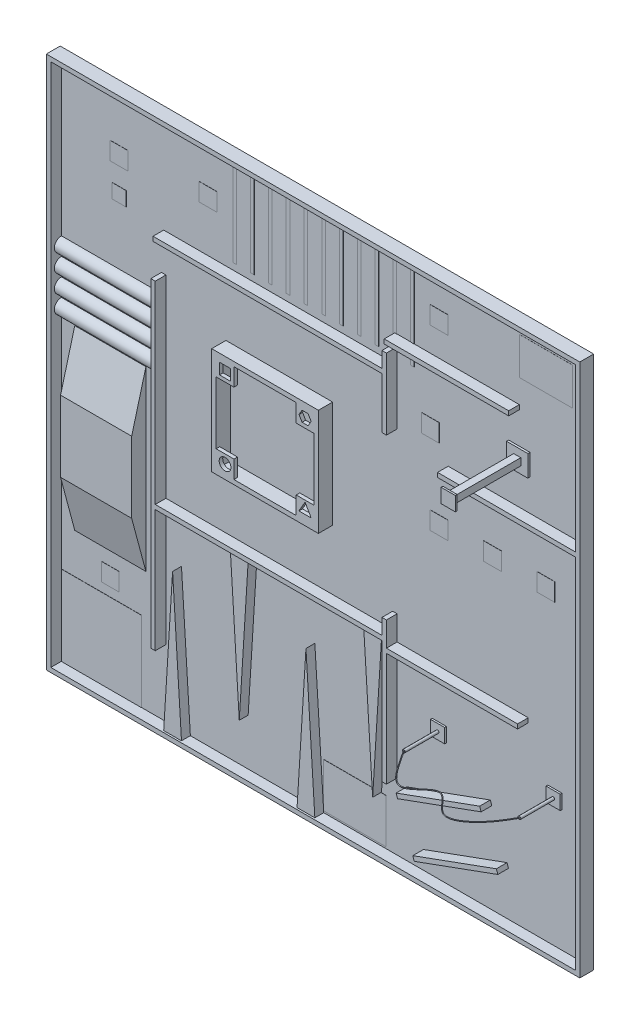
SolidWorks part; units mm, degrees
ref_plane "Front Plane" through (0, 0, 0) normal (0, 0, 1) x (1, 0, 0)
ref_plane "Top Plane" through (0, 0, 0) normal (0, 1, 0) x (1, 0, 0)
ref_plane "Right Plane" through (0, 0, 0) normal (1, 0, 0) x (0, 0, -1)
ref_plane "P_Front_m18" through (0, 0, -18) normal (0, 0, 1) x (1, 0, 0)
sketch "Sketch1" plane through (0, 0, -18) normal (0, 0, 1) x (1, 0, 0)
  line L0 (-1500, -1500) -> (1500, -1500)
  line L1 (1500, -1500) -> (1500, 1500)
  line L2 (1500, 1500) -> (-1500, 1500)
  line L3 (-1500, 1500) -> (-1500, -1500)
extrude "Board_18mm_ply" add sketch "Sketch1" along normal blind 18
sketch "Sketch2" plane through (0, 0, 0) normal (0, 0, 1) x (1, 0, 0)
  line L0 (-1500, -1500) -> (1500, -1500)
  line L1 (1500, -1500) -> (1500, 1500)
  line L2 (1500, 1500) -> (-1500, 1500)
  line L3 (-1500, 1500) -> (-1500, -1500)
  line L4 (-1475, -1475) -> (1475, -1475)
  line L5 (1475, -1475) -> (1475, 1475)
  line L6 (1475, 1475) -> (-1475, 1475)
  line L7 (-1475, 1475) -> (-1475, -1475)
extrude "Perimeter_wall" add sketch "Sketch2" along normal blind 60
sketch "Sketch3" plane through (0, 0, 0) normal (0, 0, 1) x (1, 0, 0)
  line L0 (-912.5, -1100) -> (-887.5, -1100)
  line L1 (-887.5, -1100) -> (-887.5, 700)
  line L2 (-887.5, 700) -> (-912.5, 700)
  line L3 (-912.5, 700) -> (-912.5, -1100)
extrude "Wall_1" add sketch "Sketch3" along normal blind 60
sketch "Sketch4" plane through (0, 0, 0) normal (0, 0, 1) x (1, 0, 0)
  line L0 (-900, 887.5) -> (400, 887.5)
  line L1 (400, 887.5) -> (400, 912.5)
  line L2 (400, 912.5) -> (-900, 912.5)
  line L3 (-900, 912.5) -> (-900, 887.5)
extrude "Wall_2" add sketch "Sketch4" along normal blind 60
sketch "Sketch5" plane through (0, 0, 0) normal (0, 0, 1) x (1, 0, 0)
  line L0 (387.5, 600) -> (412.5, 600)
  line L1 (412.5, 600) -> (412.5, 1000)
  line L2 (412.5, 1000) -> (387.5, 1000)
  line L3 (387.5, 1000) -> (387.5, 600)
extrude "Wall_3" add sketch "Sketch5" along normal blind 60
sketch "Sketch6" plane through (0, 0, 0) normal (0, 0, 1) x (1, 0, 0)
  line L0 (387.5, -1100) -> (412.5, -1100)
  line L1 (412.5, -1100) -> (412.5, -300)
  line L2 (412.5, -300) -> (387.5, -300)
  line L3 (387.5, -300) -> (387.5, -1100)
extrude "Wall_4" add sketch "Sketch6" along normal blind 60
sketch "Sketch7" plane through (0, 0, 0) normal (0, 0, 1) x (1, 0, 0)
  line L0 (400, 1037.5) -> (1100, 1037.5)
  line L1 (1100, 1037.5) -> (1100, 1062.5)
  line L2 (1100, 1062.5) -> (400, 1062.5)
  line L3 (400, 1062.5) -> (400, 1037.5)
extrude "Wall_5" add sketch "Sketch7" along normal blind 60
sketch "Sketch8" plane through (0, 0, 0) normal (0, 0, 1) x (1, 0, 0)
  line L0 (700, 537.5) -> (1475, 537.5)
  line L1 (1475, 537.5) -> (1475, 562.5)
  line L2 (1475, 562.5) -> (700, 562.5)
  line L3 (700, 562.5) -> (700, 537.5)
extrude "Wall_6" add sketch "Sketch8" along normal blind 60
sketch "Sketch9" plane through (0, 0, 0) normal (0, 0, 1) x (1, 0, 0)
  line L0 (400, -462.5) -> (1150, -462.5)
  line L1 (1150, -462.5) -> (1150, -437.5)
  line L2 (1150, -437.5) -> (400, -437.5)
  line L3 (400, -437.5) -> (400, -462.5)
extrude "Wall_7" add sketch "Sketch9" along normal blind 60
sketch "Sketch10" plane through (0, 0, 0) normal (0, 0, 1) x (1, 0, 0)
  line L0 (-900, -412.5) -> (387.5, -412.5)
  line L1 (387.5, -412.5) -> (387.5, -387.5)
  line L2 (387.5, -387.5) -> (-900, -387.5)
  line L3 (-900, -387.5) -> (-900, -412.5)
extrude "Wall_8" add sketch "Sketch10" along normal blind 60
sketch "Sketch11" plane through (0, 0, 0) normal (0, 0, 1) x (1, 0, 0)
  line L0 (569.3521, -1397.2512) -> (1039.1984, -1226.2411)
  line L1 (1039.1984, -1226.2411) -> (1030.6479, -1202.7488)
  line L2 (1030.6479, -1202.7488) -> (560.8016, -1373.7589)
  line L3 (560.8016, -1373.7589) -> (569.3521, -1397.2512)
extrude "Diagonal_1" add sketch "Sketch11" along normal blind 60
sketch "Sketch12" plane through (0, 0, 0) normal (0, 0, 1) x (1, 0, 0)
  line L0 (475.3521, -1139.2512) -> (945.1984, -968.2411)
  line L1 (945.1984, -968.2411) -> (936.6479, -944.7488)
  line L2 (936.6479, -944.7488) -> (466.8016, -1115.7589)
  line L3 (466.8016, -1115.7589) -> (475.3521, -1139.2512)
extrude "Diagonal_2" add sketch "Sketch12" along normal blind 60
sketch "Sketch13" plane through (0, 0, 0) normal (0, 0, 1) x (1, 0, 0)
  line L0 (-850, -1475) -> (-750, -1475)
  line L1 (-750, -1475) -> (-800, -675)
  line L2 (-800, -675) -> (-850, -1475)
extrude "Slalom_ridge_1" add sketch "Sketch13" along normal blind 50
sketch "Sketch14" plane through (0, 0, 0) normal (0, 0, 1) x (1, 0, 0)
  line L0 (-475, -412.5) -> (-375, -412.5)
  line L1 (-375, -412.5) -> (-425, -1212.5)
  line L2 (-425, -1212.5) -> (-475, -412.5)
extrude "Slalom_ridge_2" add sketch "Sketch14" along normal blind 50
sketch "Sketch15" plane through (0, 0, 0) normal (0, 0, 1) x (1, 0, 0)
  line L0 (-100, -1475) -> (0, -1475)
  line L1 (0, -1475) -> (-50, -675)
  line L2 (-50, -675) -> (-100, -1475)
extrude "Slalom_ridge_3" add sketch "Sketch15" along normal blind 50
sketch "Sketch16" plane through (0, 0, 0) normal (0, 0, 1) x (1, 0, 0)
  line L0 (275, -412.5) -> (375, -412.5)
  line L1 (375, -412.5) -> (325, -1212.5)
  line L2 (325, -1212.5) -> (275, -412.5)
extrude "Slalom_ridge_4" add sketch "Sketch16" along normal blind 50
sketch "Sketch17" plane through (0, 0, 0) normal (0, 0, 1) x (1, 0, 0)
  line L0 (-1475, -1475) -> (-1025, -1475)
  line L1 (-1025, -1475) -> (-1025, -1025)
  line L2 (-1025, -1025) -> (-1475, -1025)
  line L3 (-1475, -1025) -> (-1475, -1475)
extrude "Zone_Start" add sketch "Sketch17" along normal blind 1
sketch "Sketch18" plane through (0, 0, 0) normal (0, 0, 1) x (1, 0, 0)
  line L0 (-1250, -975) -> (-1150, -975)
  line L1 (-1150, -975) -> (-1150, -875)
  line L2 (-1150, -875) -> (-1250, -875)
  line L3 (-1250, -875) -> (-1250, -975)
extrude "Zone_Pickup_spot" add sketch "Sketch18" along normal blind 1
sketch "Sketch19" plane through (0, 0, 0) normal (0, 0, 1) x (1, 0, 0)
  line L0 (-1190, 920) -> (-1110, 920)
  line L1 (-1110, 920) -> (-1110, 1000)
  line L2 (-1110, 1000) -> (-1190, 1000)
  line L3 (-1190, 1000) -> (-1190, 920)
extrude "Zone_Touchdown_80" add sketch "Sketch19" along normal blind 1
sketch "Sketch20" plane through (0, 0, 0) normal (0, 0, 1) x (1, 0, 0)
  line L0 (-1200, 1100) -> (-1100, 1100)
  line L1 (-1100, 1100) -> (-1100, 1200)
  line L2 (-1100, 1200) -> (-1200, 1200)
  line L3 (-1200, 1200) -> (-1200, 1100)
extrude "Zone_Stack_100" add sketch "Sketch20" along normal blind 1
sketch "Sketch21" plane through (0, 0, 0) normal (0, 0, 1) x (1, 0, 0)
  line L0 (-700, 1150) -> (-600, 1150)
  line L1 (-600, 1150) -> (-600, 1250)
  line L2 (-600, 1250) -> (-700, 1250)
  line L3 (-700, 1250) -> (-700, 1150)
extrude "Zone_Longshot_spot" add sketch "Sketch21" along normal blind 1
sketch "Sketch22" plane through (0, 0, 0) normal (0, 0, 1) x (1, 0, 0)
  line L0 (600, 1200) -> (700, 1200)
  line L1 (700, 1200) -> (700, 1300)
  line L2 (700, 1300) -> (600, 1300)
  line L3 (600, 1300) -> (600, 1200)
extrude "Zone_Marker_spot" add sketch "Sketch22" along normal blind 1
sketch "Sketch23" plane through (0, 0, 0) normal (0, 0, 1) x (1, 0, 0)
  line L0 (550, 650) -> (650, 650)
  line L1 (650, 650) -> (650, 750)
  line L2 (650, 750) -> (550, 750)
  line L3 (550, 750) -> (550, 650)
extrude "Zone_Downy_target" add sketch "Sketch23" along normal blind 1
sketch "Sketch24" plane through (0, 0, 0) normal (0, 0, 1) x (1, 0, 0)
  line L0 (600, 200) -> (700, 200)
  line L1 (700, 200) -> (700, 300)
  line L2 (700, 300) -> (600, 300)
  line L3 (600, 300) -> (600, 200)
extrude "Zone_Hanoi_1" add sketch "Sketch24" along normal blind 1
sketch "Sketch25" plane through (0, 0, 0) normal (0, 0, 1) x (1, 0, 0)
  line L0 (900, 200) -> (1000, 200)
  line L1 (1000, 200) -> (1000, 300)
  line L2 (1000, 300) -> (900, 300)
  line L3 (900, 300) -> (900, 200)
extrude "Zone_Hanoi_2" add sketch "Sketch25" along normal blind 1
sketch "Sketch26" plane through (0, 0, 0) normal (0, 0, 1) x (1, 0, 0)
  line L0 (1200, 200) -> (1300, 200)
  line L1 (1300, 200) -> (1300, 300)
  line L2 (1300, 300) -> (1200, 300)
  line L3 (1200, 300) -> (1200, 200)
extrude "Zone_Hanoi_3" add sketch "Sketch26" along normal blind 1
sketch "Sketch27" plane through (0, 0, 0) normal (0, 0, 1) x (1, 0, 0)
  line L0 (0, -1465) -> (350, -1465)
  line L1 (350, -1465) -> (350, -1215)
  line L2 (350, -1215) -> (0, -1215)
  line L3 (0, -1215) -> (0, -1465)
extrude "Zone_End_350x250" add sketch "Sketch27" along normal blind 1
sketch "Sketch28" plane through (0, 0, 0) normal (0, 0, 1) x (1, 0, 0)
  line L0 (-510, 950) -> (-490, 950)
  line L1 (-490, 950) -> (-490, 1450)
  line L2 (-490, 1450) -> (-510, 1450)
  line L3 (-510, 1450) -> (-510, 950)
  line L4 (-410, 950) -> (-390, 950)
  line L5 (-390, 950) -> (-390, 1450)
  line L6 (-390, 1450) -> (-410, 1450)
  line L7 (-410, 1450) -> (-410, 950)
  line L8 (-310, 950) -> (-290, 950)
  line L9 (-290, 950) -> (-290, 1450)
  line L10 (-290, 1450) -> (-310, 1450)
  line L11 (-310, 1450) -> (-310, 950)
  line L12 (-210, 950) -> (-190, 950)
  line L13 (-190, 950) -> (-190, 1450)
  line L14 (-190, 1450) -> (-210, 1450)
  line L15 (-210, 1450) -> (-210, 950)
  line L16 (-110, 950) -> (-90, 950)
  line L17 (-90, 950) -> (-90, 1450)
  line L18 (-90, 1450) -> (-110, 1450)
  line L19 (-110, 1450) -> (-110, 950)
  line L20 (-10, 950) -> (10, 950)
  line L21 (10, 950) -> (10, 1450)
  line L22 (10, 1450) -> (-10, 1450)
  line L23 (-10, 1450) -> (-10, 950)
  line L24 (90, 950) -> (110, 950)
  line L25 (110, 950) -> (110, 1450)
  line L26 (110, 1450) -> (90, 1450)
  line L27 (90, 1450) -> (90, 950)
  line L28 (190, 950) -> (210, 950)
  line L29 (210, 950) -> (210, 1450)
  line L30 (210, 1450) -> (190, 1450)
  line L31 (190, 1450) -> (190, 950)
  line L32 (290, 950) -> (310, 950)
  line L33 (310, 950) -> (310, 1450)
  line L34 (310, 1450) -> (290, 1450)
  line L35 (290, 1450) -> (290, 950)
  line L36 (390, 950) -> (410, 950)
  line L37 (410, 950) -> (410, 1450)
  line L38 (410, 1450) -> (390, 1450)
  line L39 (390, 1450) -> (390, 950)
  line L40 (490, 950) -> (510, 950)
  line L41 (510, 950) -> (510, 1450)
  line L42 (510, 1450) -> (490, 1450)
  line L43 (490, 1450) -> (490, 950)
extrude "Longshot_lines_100mm" add sketch "Sketch28" along normal blind 1
sketch "Sketch29" plane through (0, 0, 0) normal (0, 0, 1) x (1, 0, 0)
  line L0 (1101.5, 1195) -> (1398.5, 1195)
  line L1 (1398.5, 1195) -> (1398.5, 1405)
  line L2 (1398.5, 1405) -> (1101.5, 1405)
  line L3 (1101.5, 1405) -> (1101.5, 1195)
extrude "Paper_A4_TF" add sketch "Sketch29" along normal blind 0.5
ref_plane "P_Right_m1400" through (-1400, 0, 0) normal (1, 0, 0) x (0, 0, -1)
sketch "Sketch30" plane through (-1400, 0, 0) normal (1, 0, 0) x (0, 0, -1)
  line L0 (0, -800) -> (-80, -501.4359)
  line L1 (-80, -501.4359) -> (-80, -101.4359)
  line L2 (-80, -101.4359) -> (0, 197.1281)
  line L3 (0, 197.1281) -> (0, -800)
extrude "Ramp_15deg_bridge_400" add sketch "Sketch30" along normal blind 400
ref_plane "P_Right_m1475" through (-1475, 0, 0) normal (1, 0, 0) x (0, 0, -1)
sketch "Sketch31" plane through (-1475, 0, 0) normal (1, 0, 0) x (0, 0, -1)
  line L0 (0, 217.1281) -> (0, 297.1281)
  line L1 (0, 317.1281) -> (0, 397.1281)
  line L2 (0, 417.1281) -> (0, 497.1281)
  line L3 (0, 517.1281) -> (0, 597.1281)
  arc A0 (0, 297.1281) -> (0, 217.1281) centre (0, 257.1281) ccw
  arc A1 (0, 397.1281) -> (0, 317.1281) centre (0, 357.1281) ccw
  arc A2 (0, 497.1281) -> (0, 417.1281) centre (0, 457.1281) ccw
  arc A3 (0, 597.1281) -> (0, 517.1281) centre (0, 557.1281) ccw
extrude "Speed_breakers_R40" add sketch "Sketch31" along normal blind 562.5
sketch "Sketch32" plane through (0, 0, 0) normal (0, 0, 1) x (1, 0, 0)
  line L0 (1040, 740) -> (1160, 740)
  line L1 (1160, 740) -> (1160, 860)
  line L2 (1160, 860) -> (1040, 860)
  line L3 (1040, 860) -> (1040, 740)
extrude "Pole_foot" add sketch "Sketch32" along normal blind 12
ref_plane "P_Front_12" through (0, 0, 12) normal (0, 0, 1) x (1, 0, 0)
sketch "Sketch33" plane through (0, 0, 12) normal (0, 0, 1) x (1, 0, 0)
  line L0 (1080, 780) -> (1120, 780)
  line L1 (1120, 780) -> (1120, 820)
  line L2 (1120, 820) -> (1080, 820)
  line L3 (1080, 820) -> (1080, 780)
extrude "Pole_post" add sketch "Sketch33" along normal blind 378
ref_plane "P_Front_390" through (0, 0, 390) normal (0, 0, 1) x (1, 0, 0)
sketch "Sketch34" plane through (0, 0, 390) normal (0, 0, 1) x (1, 0, 0)
  line L0 (1060, 760) -> (1140, 760)
  line L1 (1140, 760) -> (1140, 840)
  line L2 (1140, 840) -> (1060, 840)
  line L3 (1060, 840) -> (1060, 760)
extrude "Pole_top_400" add sketch "Sketch34" along normal blind 10
sketch "Sketch35" plane through (0, 0, 0) normal (0, 0, 1) x (1, 0, 0)
  line L0 (-550, -50) -> (50, -50)
  line L1 (50, -50) -> (50, 550)
  line L2 (50, 550) -> (-550, 550)
  line L3 (-550, 550) -> (-550, -50)
  line L4 (-525, -25) -> (25, -25)
  line L5 (25, -25) -> (25, 525)
  line L6 (25, 525) -> (-525, 525)
  line L7 (-525, 525) -> (-525, -25)
extrude "Escape_box_600" add sketch "Sketch35" along normal blind 80
ref_plane "P_Front_60" through (0, 0, 60) normal (0, 0, 1) x (1, 0, 0)
sketch "Sketch36" plane through (0, 0, 60) normal (0, 0, 1) x (1, 0, 0)
  line L0 (-525, -25) -> (-425, -25)
  line L1 (-425, -25) -> (-425, 75)
  line L2 (-425, 75) -> (-525, 75)
  line L3 (-525, 75) -> (-525, -25)
  line L4 (-525, 425) -> (-425, 425)
  line L5 (-425, 425) -> (-425, 525)
  line L6 (-425, 525) -> (-525, 525)
  line L7 (-525, 525) -> (-525, 425)
  line L8 (-75, -25) -> (25, -25)
  line L9 (25, -25) -> (25, 75)
  line L10 (25, 75) -> (-75, 75)
  line L11 (-75, 75) -> (-75, -25)
  line L12 (-75, 425) -> (25, 425)
  line L13 (25, 425) -> (25, 525)
  line L14 (25, 525) -> (-75, 525)
  line L15 (-75, 525) -> (-75, 425)
extrude "Escape_corner_plates" add sketch "Sketch36" along normal blind 20
ref_plane "P_Front_59" through (0, 0, 59) normal (0, 0, 1) x (1, 0, 0)
sketch "Sketch37" plane through (0, 0, 59) normal (0, 0, 1) x (1, 0, 0)
  line L0 (-506, 444) -> (-444, 444)
  line L1 (-444, 444) -> (-444, 506)
  line L2 (-444, 506) -> (-506, 506)
  line L3 (-506, 506) -> (-506, 444)
  line L4 (-25, 65) -> (-59.641, 5)
  line L5 (-59.641, 5) -> (9.641, 5)
  line L6 (9.641, 5) -> (-25, 65)
  line L7 (9, 475) -> (-8, 504.4449)
  line L8 (-8, 504.4449) -> (-42, 504.4449)
  line L9 (-42, 504.4449) -> (-59, 475)
  line L10 (-59, 475) -> (-42, 445.5551)
  line L11 (-42, 445.5551) -> (-8, 445.5551)
  line L12 (-8, 445.5551) -> (9, 475)
  circle A0 centre (-475, 25) radius 33
extrude "Escape_shape_holes" cut sketch "Sketch37" along normal blind 30
sketch "Sketch38" plane through (0, 0, 0) normal (0, 0, 1) x (1, 0, 0)
  circle A0 centre (650, -750) radius 8
  circle A1 centre (1300, -750) radius 8
extrude "Buzz_posts" add sketch "Sketch38" along normal blind 200
sketch "Sketch39" plane through (0, 0, 0) normal (0, 0, 1) x (1, 0, 0)
  line L0 (610, -790) -> (690, -790)
  line L1 (690, -790) -> (690, -710)
  line L2 (690, -710) -> (610, -710)
  line L3 (610, -710) -> (610, -790)
  line L4 (1260, -790) -> (1340, -790)
  line L5 (1340, -790) -> (1340, -710)
  line L6 (1340, -710) -> (1260, -710)
  line L7 (1260, -710) -> (1260, -790)
extrude "Buzz_feet" add sketch "Sketch39" along normal blind 10
ref_plane "P_Top_m750" through (0, -750, 0) normal (0, 1, 0) x (1, 0, 0)
sketch "Sketch40" plane through (0, -750, 0) normal (0, 1, 0) x (1, 0, 0)
  spline S0 degree 3 poles (650, -200) (668.3967, -228.3384) (710.9661, -293.9125) (820.9563, -442.4448) (955.7098, -224.7876) (1060.4217, -453.958) (1226.702, -329.6386) (1275.3721, -243.5582) (1300, -200) knots 0 0 0 0 0.12455 0.288205 0.463969 0.640204 0.817937 1 1 1 1
sweep "Sweep1" add path "Sketch40" circular profile diameter 4 parameters "D3"=4
